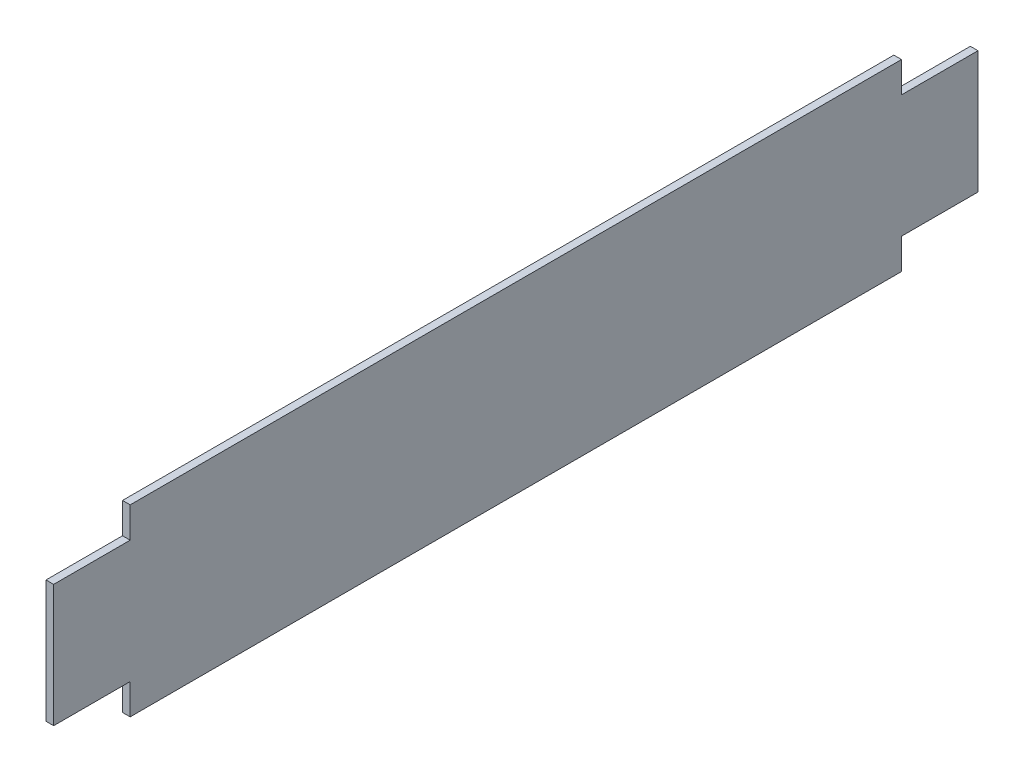
SolidWorks part; units mm, degrees
ref_plane "Front" through (0, 0, 0) normal (0, 0, 1) x (1, 0, 0)
ref_plane "Top" through (0, 0, 0) normal (0, 1, 0) x (1, 0, 0)
ref_plane "Right" through (0, 0, 0) normal (1, 0, 0) x (0, 0, -1)
sketch "Sketch1" plane through (0, 0, 0) normal (0, 0, 1) x (1, 0, 0)
  line L1 (-1.5875, 25.4) -> (1.5875, 25.4)
  line L2 (-1.5875, 25.4) -> (-1.5875, -25.4)
  line L3 (-1.5875, -25.4) -> (1.5875, -25.4)
  line L4 (1.5875, 25.4) -> (1.5875, -25.4)
  line L5 (-1.5875, 25.4) -> (1.5875, -25.4) construction
  line L6 (-1.5875, -25.4) -> (1.5875, 25.4) construction
  line L7 (-1.5875, 38.1) -> (1.5875, 38.1)
  line L8 (-1.5875, 38.1) -> (-1.5875, -38.1)
  line L9 (-1.5875, -38.1) -> (1.5875, -38.1)
  line L10 (1.5875, 38.1) -> (1.5875, -38.1)
  line L11 (-1.5875, 38.1) -> (1.5875, -38.1) construction
  line L12 (-1.5875, -38.1) -> (1.5875, 38.1) construction
  point P0 (0, 0)
  point P6 (0, 0)
  dimension "D1" = 3.175
  dimension "D2" = 50.8
  dimension "D3" = 76.2
extrude "Boss-Extrude1" add sketch "Sketch1" along normal mid plane 383.54 contours L4 L1 L2 L3 region at (0, 0, 0)
extrude "Boss-Extrude2" add sketch "Sketch1<3>" along normal mid plane 320.04 contours L10 L7 L8 L1 | L10 L3 L8 L9 region at (0, 31.75, 0) region at (0, -31.75, 0)
sketch "Sketch1<3>" plane through (0, 0, 0) normal (0, 0, 1) x (1, 0, 0) same geometry as "Sketch1"
sketch "Sketch3" plane through (1.5875, 0, 0) normal (1, 0, 0) x (0, 0, -1)
  line L0 (0, 1.7463) -> (0, -1.7463) construction
  circle A0 centre (-126.5143, 8.4304) radius 2.55
  circle A1 centre (126.5143, 8.4304) radius 2.55
  dimension "D1" = 5.1
extrude "Cut-Extrude1" [suppressed] cut sketch "Sketch3" against normal through all contours A0 | A1
